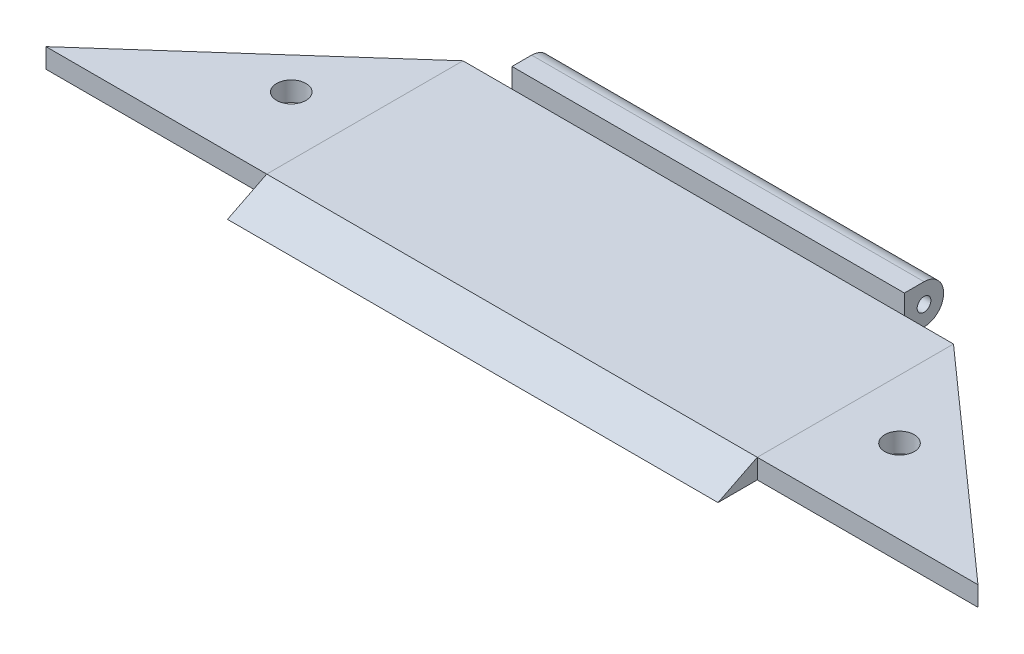
SolidWorks part; units mm, degrees
ref_plane "前视基准面" through (0, 0, 0) normal (0, 0, 1) x (1, 0, 0)
ref_plane "上视基准面" through (0, 0, 0) normal (0, 1, 0) x (1, 0, 0)
ref_plane "右视基准面" through (0, 0, 0) normal (1, 0, 0) x (0, 0, -1)
sketch "草图1" plane through (0, 0, 0) normal (1, 0, 0) x (0, 0, -1)
  line L0 (-87.0655, 0) -> (152.9345, 0)
  line L1 (152.9345, 0) -> (152.9345, 20)
  line L2 (152.9345, 20) -> (-47.0655, 20)
  line L3 (-47.0655, 20) -> (-87.0655, 0)
  line L4 (-87.0655, 0) -> (-87.8499, 0.5883)
  line L6 (152.9345, 0) -> (192.9345, 0)
  line L7 (152.9345, 0) -> (152.9345, 40)
  line L8 (152.9345, 40) -> (192.9345, 40)
  line L9 (192.9345, 0) -> (192.9345, 40)
  circle A0 centre (172.9345, 20) radius 7
  dimension "D1" = 200
  dimension "D2" = 240
  dimension "D3" = 20
  dimension "D4" = 40
  dimension "D5" = 40
extrude "凸台-拉伸1" add sketch "草图1" along normal blind 500 contours L6 L9 L8 L7 L1 A0 | L2 L3 L0 L1 region at (0, 9.697, -42.6315) region at (0, 10, -153.5002)
sketch "草图2" plane through (0, 40, 0) normal (0, 1, 0) x (1, 0, 0)
  line L0 (500, 192.9345) -> (0, 192.9345) construction
  line L5 (500, 152.9345) -> (0, 152.9345) construction
  line L8 (0, 192.9345) -> (50, 192.9345)
  line L9 (0, 192.9345) -> (0, 152.9345)
  line L10 (0, 152.9345) -> (50, 152.9345)
  line L11 (50, 192.9345) -> (50, 152.9345)
  line L12 (450, 192.9345) -> (500, 192.9345)
  line L13 (450, 192.9345) -> (450, 152.9345)
  line L14 (450, 152.9345) -> (500, 152.9345)
  line L15 (500, 192.9345) -> (500, 152.9345)
  dimension "D1" = 400
  dimension "D2" = 50
  dimension "D3" = 40
  dimension "D4" = 50
extrude "切除-拉伸1" cut sketch "草图2" against normal blind 500
sketch "草图3" plane through (0, 20, 0) normal (0, 1, 0) x (1, 0, 0)
  line L0 (500, -47.0655) -> (725, -47.0655)
  line L1 (500, 152.9345) -> (725, -47.0655)
  line L2 (500, 152.9345) -> (500, -47.0655) construction
  line L3 (250, -47.0655) -> (250, 37.9345) construction
  line L4 (500, -47.0655) -> (0, -47.0655) construction
  line L5 (0, 152.9345) -> (-225, -47.0655)
  line L6 (0, -47.0655) -> (-225, -47.0655)
  circle A0 centre (560, 37.9345) radius 15
  circle A1 centre (-60, 37.9345) radius 15
  line M1 (0, 152.9345) -> (0, -47.0655)
  line M3 (500, -47.0655) -> (500, 152.9345)
  dimension "D2" = 30
  dimension "D1" = 225
  dimension "D3" = 60
  dimension "D4" = 85
extrude "凸台-拉伸2" add sketch "草图3" against normal blind 20 separate body contours M1 | L0 A0 M3 region at (575.4865, 20, -19.0065) region at (-75.4865, 20, -19.0065)
fillet "圆角2" radius 20 2 edges at (250, 0, -192.9345) (250, 40, -192.9345) tangent propagation no
